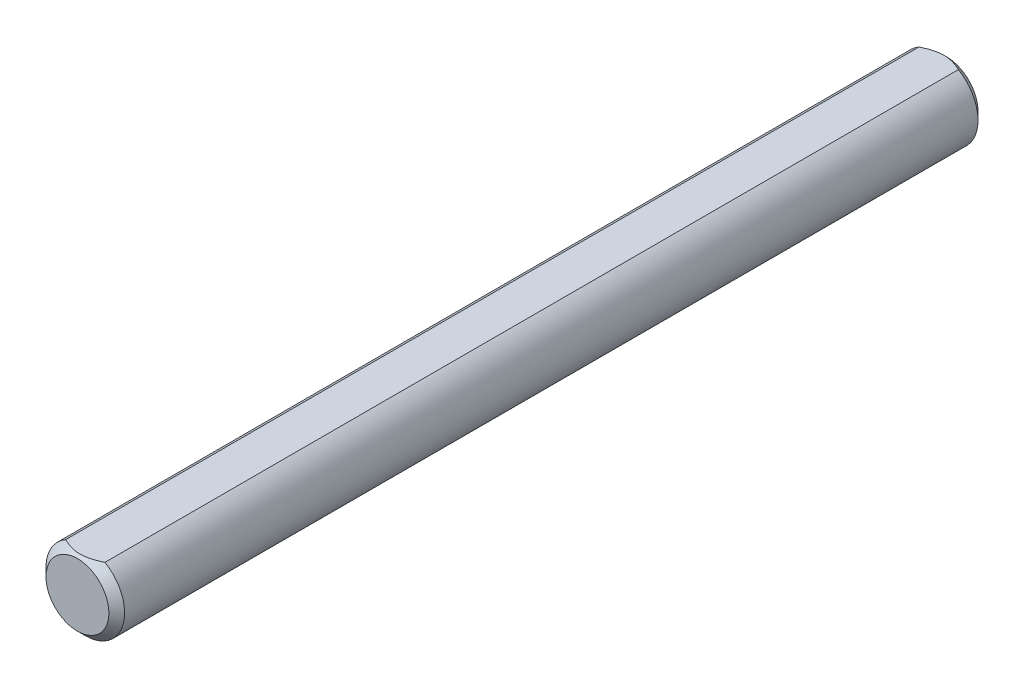
SolidWorks part; units mm, degrees
ref_plane "Front" through (0, 0, 0) normal (0, 0, 1) x (1, 0, 0)
ref_plane "Top" through (0, 0, 0) normal (0, 1, 0) x (1, 0, 0)
ref_plane "Right" through (0, 0, 0) normal (1, 0, 0) x (0, 0, -1)
sketch "Sketch1" plane through (0, 0, 0) normal (0, 0, 1) x (1, 0, 0)
  circle A0 centre (0, 0) radius 3.175
  dimension "D1" = 6.35
extrude "Extrude1" add sketch "Sketch1" along normal mid plane 70.1675
chamfer "Chamfer1" distance 0.635 angle 45 2 edges at (3.175, 0, -35.0838) (3.175, 0, 35.0838)
sketch "Sketch13" plane through (0, 0, 0) normal (0, 0, 1) x (1, 0, 0)
  line L3 (-1.5875, 2.7496) -> (1.5875, 2.7496)
  circle A0 centre (0, 0) radius 3.175 construction
  arc A1 (1.5875, 2.7496) -> (-1.5875, 2.7496) centre (0, 0) ccw
  dimension "D1" = 3.175
extrude "Extrude7" cut sketch "Sketch13" against normal through all and the other way through all
equation "\"D1@Chamfer1\" = \"D1@Sketch1\" * .1"
equation "\"D1@Sketch13\" = \"D1@Sketch1\" * .5"
